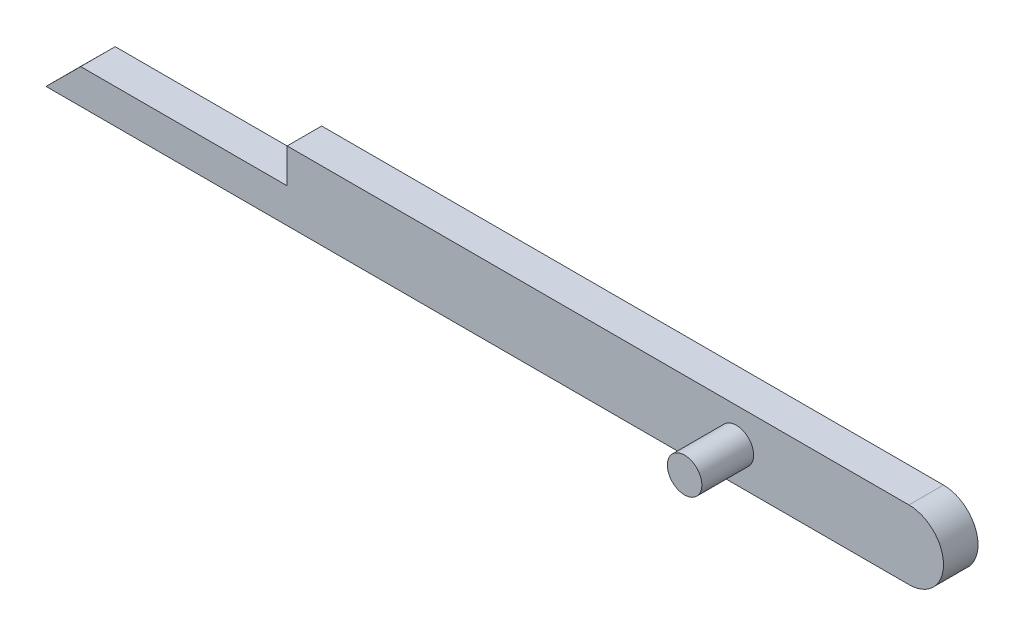
SolidWorks part; units mm, degrees
ref_plane "Front Plane" through (0, 0, 0) normal (0, 0, 1) x (1, 0, 0)
ref_plane "Top Plane" through (0, 0, 0) normal (0, 1, 0) x (1, 0, 0)
ref_plane "Right Plane" through (0, 0, 0) normal (1, 0, 0) x (0, 0, -1)
sketch "Sketch1" plane through (0, 0, 0) normal (0, 0, 1) x (1, 0, 0)
  line L0 (-229.9142, 0) -> (-110.2832, 0)
  line L1 (-110.2832, 20) -> (250, 20)
  line L2 (-250, -20) -> (250, -20)
  line L3 (-110.2832, 0) -> (-110.2832, 20)
  line L4 (-229.9142, 0) -> (-250, -20)
  arc A1 (250, -20) -> (250, 20) centre (250, 0) ccw
  circle A2 centre (150, 0) radius 10
  point P2 (0, 0)
  dimension "D1" = 500
extrude "Boss-Extrude1" add sketch "Sketch1" along normal blind 20
extrude "Boss-Extrude2" add sketch "Sketch1<2>" along normal blind 50 contours A2
sketch "Sketch1<2>" plane through (0, 0, 0) normal (0, 0, 1) x (1, 0, 0) same geometry as "Sketch1"
